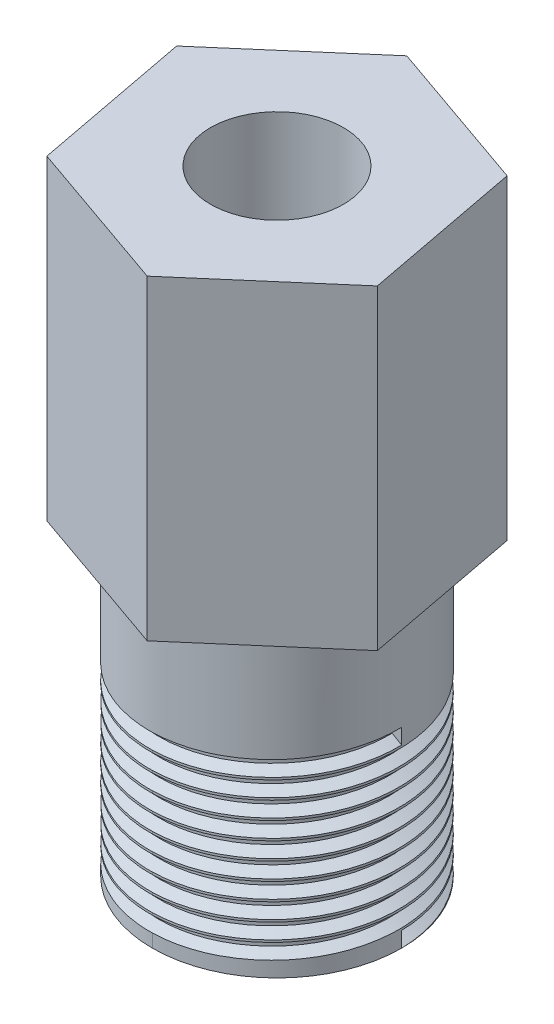
SolidWorks part; units mm, degrees
ref_plane "Front Plane" through (0, 0, 0) normal (0, 0, 1) x (1, 0, 0)
ref_plane "Top Plane" through (0, 0, 0) normal (0, 1, 0) x (1, 0, 0)
ref_plane "Right Plane" through (0, 0, 0) normal (1, 0, 0) x (0, 0, -1)
sketch "Szkic1" plane through (0, 0, 0) normal (0, 0, 1) x (1, 0, 0)
  line L0 (0, 0) -> (-7.5, 0)
  line L1 (-7.5, 0) -> (-7.5, 12)
  line L2 (-7.5, 12) -> (0, 12)
  line L3 (0, 12) -> (0, 0)
  line L4 (-7.5, 12) -> (-7.5, 16)
  line L5 (-7.5, 16) -> (0, 16)
  line L6 (0, 16) -> (0, 12)
  line L7 (-7.5, 16) -> (-7.5, 37)
  line L8 (-7.5, 37) -> (-4, 37)
  line L9 (-4, 37) -> (-4, 16)
  line L10 (-7.5, 12) -> (-7.5, 16)
  line L12 (-7.5, 12) -> (0, 12)
  line L13 (-7.5, 12) -> (-7.5, 16)
  line L14 (-7.5, 16) -> (0, 16)
  line L15 (0, 12) -> (0, 16)
  line L16 (-7.5, 16) -> (-4, 16)
  line L17 (-7.5, 16) -> (-7.5, 37)
  line L18 (-7.5, 37) -> (-4, 37)
  line L19 (-4, 16) -> (-4, 37)
  dimension "D1" = 7.5
  dimension "D2" = 4
  dimension "D3" = 12
  dimension "D4" = 4
  dimension "D5" = 37
revolve "Obrót1" add sketch "Szkic1" angle 360 about L3 region at (-3.75, 6, 0) region at (-3.75, 14, 0) region at (-5.75, 26.5, 0)
sketch "Szkic2" plane through (0, 37, 0) normal (0, 1, 0) x (1, 0, 0)
  line L1 (-9.2675, 3.2321) -> (-7.4328, -6.4099)
  line L2 (-7.4328, -6.4099) -> (1.8347, -9.6419)
  line L3 (1.8347, -9.6419) -> (9.2675, -3.2321)
  line L4 (9.2675, -3.2321) -> (7.4328, 6.4099)
  line L5 (7.4328, 6.4099) -> (-1.8347, 9.6419)
  line L6 (-1.8347, 9.6419) -> (-9.2675, 3.2321)
  circle A0 centre (0, 0) radius 8.5 construction
  circle A1 centre (0, 0) radius 4
  point P10 (0, 0)
  dimension "D1" = 17
extrude "Dodanie-wyciągnięcie1" add sketch "Szkic2" against normal blind 19
thread "Gwint1" pitch 1.0583 method cut profile "Thread Profile1" start angle 0, offset 0, length 0, pitch 1.0583, diameter 15
ref_plane "Płaszczyzna1" through (7.5, 0, 0) normal (0, 0, 1) x (1, 0, 0)
sketch "Thread Profile1" plane through (7.5, 0, 0) normal (0, 0, 1) x (1, 0, 0)
  line L0 (0, 0) -> (0, 1.0583) construction
  line L11 (0, 0) -> (0, 0.926)
  line L12 (0, 0.926) -> (-0.5728, 0.5953)
  line L13 (-0.5728, 0.5953) -> (-0.5728, 0.3307)
  line L15 (-0.5728, 0.3307) -> (0, 0)
  line L17 (-0.5728, 0.463) -> (0, 0.463) construction
  point P2 (0, 0)
  dimension "Pitch" = 1.0583
  dimension "Profile_Angle" = 60
  dimension "Profile_Land" = 0.2646
  dimension "Profile_Height" = 0.5728
extrude "Wytnij-wyciągnięcie1" cut sketch "Szkic2<4>" against normal blind 91 contours A1
sketch "Szkic2<4>" plane through (0, 37, 0) normal (0, 1, 0) x (1, 0, 0) same geometry as "Szkic2"
